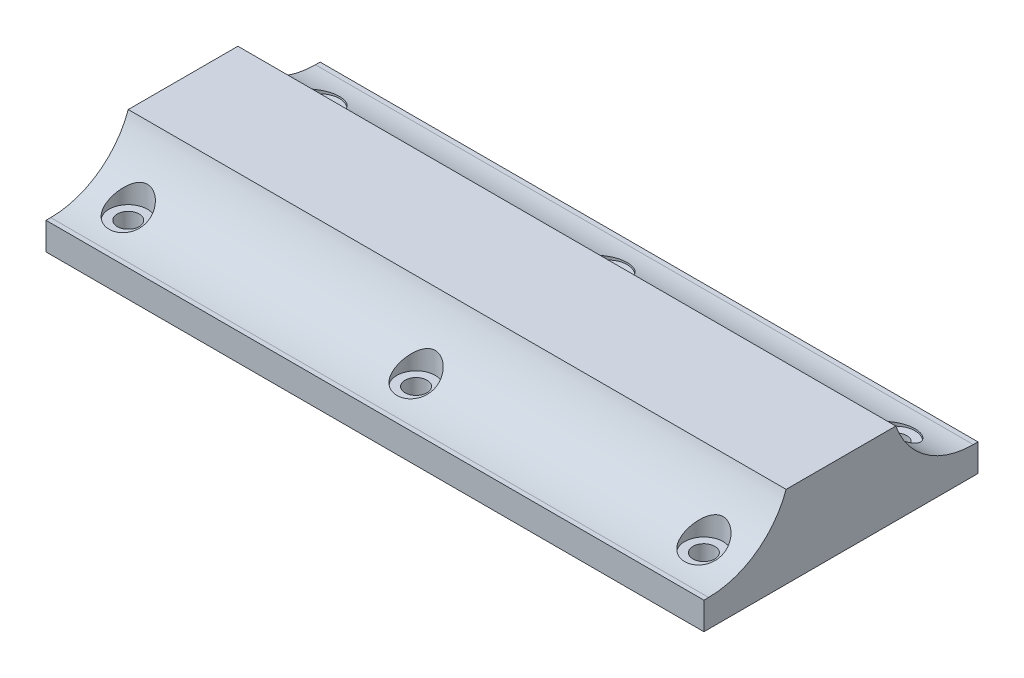
SolidWorks part; units mm, degrees
ref_plane "Front Plane" through (0, 0, 0) normal (0, 0, 1) x (1, 0, 0)
ref_plane "Top Plane" through (0, 0, 0) normal (0, 1, 0) x (1, 0, 0)
ref_plane "Right Plane" through (0, 0, 0) normal (1, 0, 0) x (0, 0, -1)
sketch "Sketch2" plane through (0, 0, 0) normal (0, 1, 0) x (1, 0, 0)
  line L0 (-46.8981, 34.5466) -> (-46.8981, -15.4534)
  line L1 (-46.8981, -15.4534) -> (73.1019, -15.4534)
  line L2 (73.1019, -15.4534) -> (73.1019, 34.5466)
  line L3 (73.1019, 34.5466) -> (-46.8981, 34.5466)
  dimension "D1" = 120
  dimension "D2" = 50
extrude "Boss-Extrude1" add sketch "Sketch2" along normal blind 15
sketch "Sketch3" plane through (0, 0, 0) normal (0, 1, 0) x (1, 0, 0)
  line L0 (74.3548, 9.5466) -> (-56.2815, 9.5466) construction
  line L1 (63.1019, 9.5466) -> (63.1019, 17.0466)
  line L2 (63.1019, 17.0466) -> (3.1019, 17.0466)
  line L3 (3.1019, 17.0466) -> (3.1019, 19.5466)
  line L4 (3.1019, 19.5466) -> (-36.8981, 19.5466)
  line L5 (-36.8981, 19.5466) -> (-36.8981, 9.5466)
  line L6 (-36.8981, 9.5466) -> (63.1019, 9.5466)
  line L7 (73.1019, -15.4534) -> (73.1019, 34.5466) construction
  line L9 (-46.8981, -15.4534) -> (73.1019, -15.4534) construction
  dimension "D1" = 60
  dimension "D2" = 40
  dimension "D3" = 10
  dimension "D4" = 25
  dimension "D5" = 10
  dimension "D6" = 7.5
sketch "Skizze7" plane through (-46.8981, 0, 0) normal (-1, 0, 0) x (0, 0, 1)
  line L1 (-34.5466, 0) -> (15.4534, 0) construction
  line L3 (-9.5466, -6.0172) -> (-9.5466, 6.0172) construction
  line L4 (15.4534, 15) -> (15.4534, 0) construction
  line L5 (-34.5466, 15) -> (-34.5466, 0) construction
  circle A0 centre (-9.5466, 2.5) radius 1.5
  dimension "D1" = 3
  dimension "D2" = 2.5
extrude "Schnitt-Linear austragen6" cut sketch "Skizze7" against normal blind 10
revolve "Schnitt-Rotation1" cut sketch "Sketch3" angle 360 about L0
sketch "Skizze10" plane through (0, 0, 0) normal (0, -1, 0) x (1, 0, 0)
  line L0 (63.1019, -17.0466) -> (3.1019, -17.0466) construction
  line L1 (53.1019, -17.0466) -> (40.6019, -17.0466)
  line L2 (53.1019, -17.0466) -> (53.1019, -15.5466)
  line L3 (53.1019, -15.5466) -> (40.6019, -15.5466)
  line L4 (40.6019, -17.0466) -> (40.6019, -15.5466)
  line L5 (63.1019, -2.0466) -> (63.1019, -17.0466) construction
  line L10 (85.7448, -9.5466) -> (-66.8579, -9.5466) construction
  line L11 (-46.8981, 15.4534) -> (73.1019, 15.4534) construction
  line L12 (73.1019, -34.5466) -> (-46.8981, -34.5466) construction
  dimension "D1" = 10
  dimension "D2" = 12.5
  dimension "D5" = 1.5
revolve "Rotation3" add sketch "Skizze10" angle 180 about L10 reverse direction yes
sketch "Skizze11" plane through (0, 0, 0) normal (0, -1, 0) x (1, 0, 0)
  line L0 (40.6019, -17.0466) -> (3.1019, -17.0466) construction
  line L1 (28.1019, -17.0466) -> (15.6019, -17.0466)
  line L2 (28.1019, -17.0466) -> (28.1019, -15.5466)
  line L3 (28.1019, -15.5466) -> (15.6019, -15.5466)
  line L4 (15.6019, -17.0466) -> (15.6019, -15.5466)
  line L5 (53.1019, -15.5466) -> (40.6019, -15.5466) construction
  line L6 (40.6019, -15.5466) -> (40.6019, -17.0466) construction
  line L7 (95.0378, -9.5466) -> (-94.5432, -9.5466) construction
  line L8 (-46.8981, 15.4534) -> (73.1019, 15.4534) construction
  line L9 (73.1019, -34.5466) -> (-46.8981, -34.5466) construction
  point P10 (40.6019, -16.2966)
  dimension "D1" = 12.5
  dimension "D2" = 12.5
revolve "Rotation4" add sketch "Skizze11" angle 180 about L7 reverse direction yes
sketch "Skizze12" plane through (0, 0, 0) normal (0, -1, 0) x (1, 0, 0)
  line L0 (73.1019, 15.4534) -> (73.1019, -34.5466) construction
  line L1 (-46.8981, -34.5466) -> (-46.8981, 15.4534) construction
  line L3 (-46.8981, 15.4534) -> (73.1019, 15.4534) construction
  circle A0 centre (-39.3981, 7.9534) radius 2
  circle A1 centre (13.1019, 7.9534) radius 2
  circle A2 centre (65.6019, 7.9534) radius 2
  dimension "D3" = 4
  dimension "D2" = 7.5
  dimension "D4" = 7.5
  dimension "D5" = 7.5
  dimension "D1" = 3
ref_plane "Ebene6" through (0, 0, -9.5466) normal (0, 0, 1) x (1, 0, 0)
extrude "Schnitt-Linear austragen7" cut sketch "Skizze12" against normal through all
mirror "Spiegeln1" about plane through (0, 0, -9.5466) normal (0, 0, 1) of "Schnitt-Linear austragen7"
sketch "Skizze13" plane through (-46.8981, 0, 0) normal (-1, 0, 0) x (0, 0, 1)
  line L0 (-34.5466, 0) -> (15.4534, 0) construction
  line L1 (15.4534, 15) -> (0.4534, 15)
  line L2 (15.4534, 15) -> (15.4534, 5)
  line L3 (15.4534, 5) -> (0.4534, 5)
  line L4 (0.4534, 15) -> (0.4534, 5)
  line L5 (-34.5466, 0) -> (15.4534, 0) construction
  line L6 (-34.5466, 15) -> (-19.5466, 15)
  line L7 (-34.5466, 15) -> (-34.5466, 5)
  line L8 (-34.5466, 5) -> (-19.5466, 5)
  line L9 (-19.5466, 15) -> (-19.5466, 5)
  dimension "D1" = 15
  dimension "D2" = 5
  dimension "D3" = 15
  dimension "D4" = 5
extrude "Schnitt-Linear austragen8" cut sketch "Skizze13" against normal through all contours L2 L1 L4 L3 | L7 L6 L9 L8
fillet "Fillet1" radius 15 1 edges at (13.1019, 5, 0.4534)
fillet "Fillet2" radius 15 1 edges at (13.1019, 5, -19.5466)
ref_plane "Plane1" through (0, 25, 0) normal (0, 1, 0) x (1, 0, 0)
sketch "Sketch4" plane through (0, 25, 0) normal (0, 1, 0) x (1, 0, 0)
  circle A0 centre (-39.3981, 27.0466) radius 3.5
  circle A1 centre (13.1019, 27.0466) radius 3.5
  circle A2 centre (13.1019, -7.9534) radius 3.5
  circle A3 centre (-39.3981, -7.9534) radius 3.5
  circle A5 centre (65.6019, -7.9534) radius 3.5
  circle A6 centre (65.6019, 27.0466) radius 3.5
  dimension "D1" = 7
  dimension "D2" = 7
  dimension "D3" = 7
  dimension "D4" = 7
  dimension "D5" = 7
  dimension "D6" = 7
extrude "Cut-Extrude1" cut sketch "Sketch4" against normal blind 20
